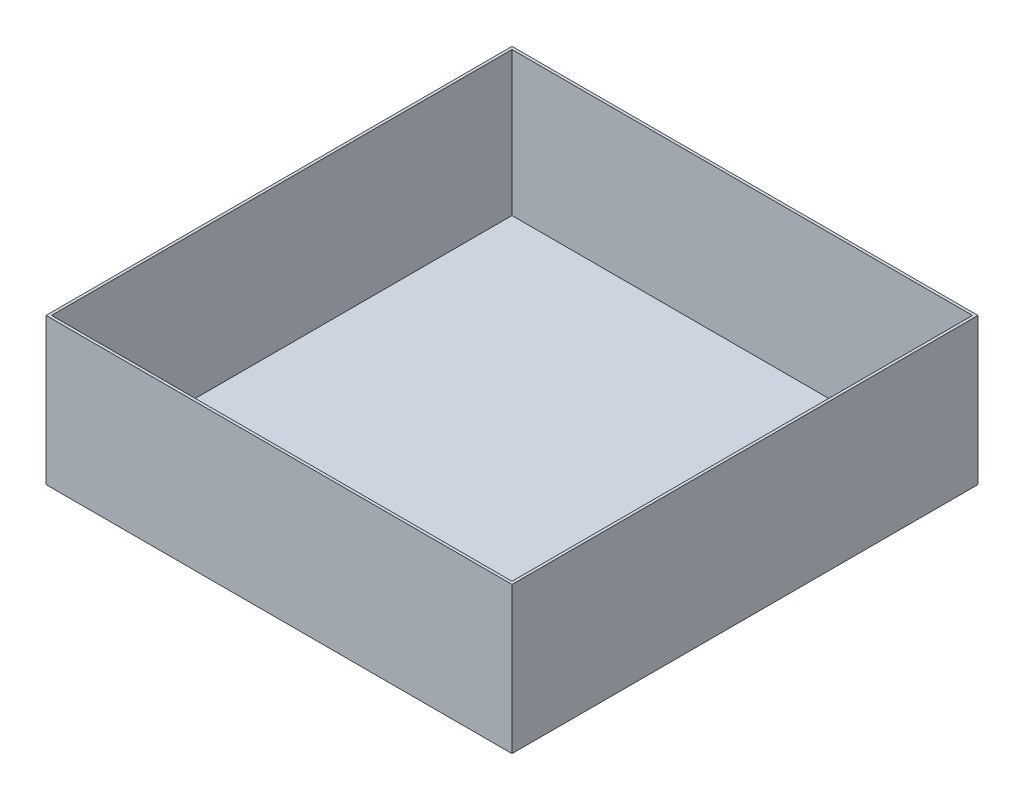
SolidWorks part; units mm, degrees
ref_plane "Front Plane" through (0, 0, 0) normal (0, 0, 1) x (1, 0, 0)
ref_plane "Top Plane" through (0, 0, 0) normal (0, 1, 0) x (1, 0, 0)
ref_plane "Right Plane" through (0, 0, 0) normal (1, 0, 0) x (0, 0, -1)
sketch "Sketch1" plane through (0, 0, 0) normal (0, 1, 0) x (1, 0, 0)
  line L1 (-838.2, -838.2) -> (838.2, -838.2)
  line L2 (-838.2, -838.2) -> (-838.2, 838.2)
  line L3 (-838.2, 838.2) -> (838.2, 838.2)
  line L4 (838.2, -838.2) -> (838.2, 838.2)
  line L5 (-838.2, -838.2) -> (838.2, 838.2) construction
  line L6 (-838.2, 838.2) -> (838.2, -838.2) construction
  point P0 (0, 0)
  dimension "D1" = 1676.4
extrude "Boss-Extrude1" add sketch "Sketch1" along normal blind 10
extrude "Extrude-Thin1" add sketch "Sketch1<2>" along normal blind 533.4 thin thin type one direction wall 10
sketch "Sketch1<2>" plane through (0, 0, 0) normal (0, 1, 0) x (1, 0, 0) same geometry as "Sketch1"
